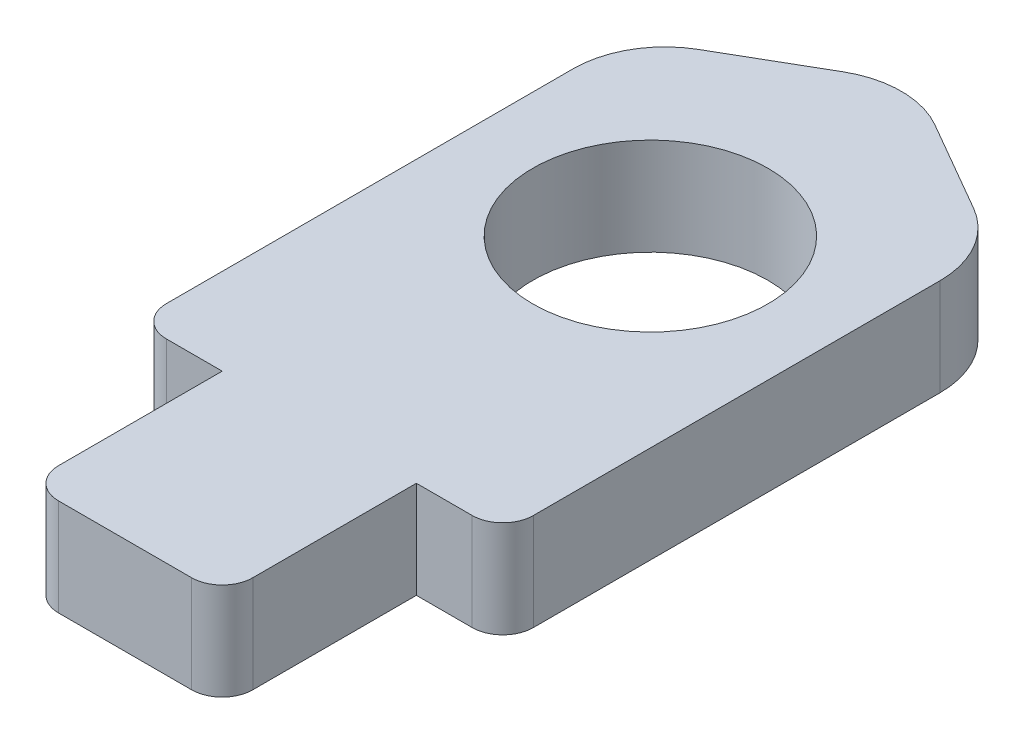
SolidWorks part; units mm, degrees
material "Beech"
ref_plane "Front Plane" through (0, 0, 0) normal (0, 0, 1) x (1, 0, 0)
ref_plane "Top Plane" through (0, 0, 0) normal (0, 1, 0) x (1, 0, 0)
ref_plane "Right Plane" through (0, 0, 0) normal (1, 0, 0) x (0, 0, -1)
sketch "Sketch2" plane through (0, 0, 0) normal (0, 1, 0) x (1, 0, 0)
  line L0 (-6, 5.205) -> (-5.4495, 5.205)
  line L1 (-6, 3.4729) -> (-6, -10.8257)
  line L2 (6, 3.4729) -> (6, -10.8257)
  line L3 (-6, -10.8257) -> (-3.175, -10.8257)
  line L4 (-4.5, 6.071) -> (-1.5, 7.8031)
  line L5 (-3.175, -10.8257) -> (-3.175, -17.1757)
  line L6 (-3.175, -17.1757) -> (3.175, -17.1757)
  line L7 (3.175, -17.1757) -> (3.175, -10.8257)
  line L8 (1.5, 7.8031) -> (4.5, 6.071)
  line L9 (3.175, -10.8257) -> (6, -10.8257)
  line L12 (5.4495, 5.205) -> (6, 5.205)
  circle A0 centre (0, 0) radius 3.845
  arc A1 (-4.5, 6.071) -> (-6, 3.4729) centre (-3, 3.4729) ccw
  arc A2 (4.5, 6.071) -> (6, 3.4729) centre (3, 3.4729) cw
  arc A3 (1.5, 7.8031) -> (-1.5, 7.8031) centre (0, 5.205) ccw
  point P3 (0, 5.205)
  point P14 (0, -17.1757)
  dimension "D1" = 7.69
  dimension "D9" = 3
  dimension "D10" = 3
  dimension "D11" = 3
  dimension "D2" = 5.205
  dimension "D3" = 16.0307
  dimension "D4" = 12
  dimension "D5" = 6.35
  dimension "D6" = 6.35
  dimension "D8" = 30
extrude "MotorMount_Extrude" add sketch "Sketch2" along normal blind 3.175 contours L8 A3 L4 A1 L1 L5 L2 A2 A0 region at (0, 0, 4.7761)
fillet "MotorMount_CornerFillet" radius 1 4 edges at (6, 1.5875, 10.8257) (-6, 1.5875, 10.8257) (-3.175, 1.5875, 17.1757) (3.175, 1.5875, 17.1757)
equation "\"CageLeftBottomEdge\"=22.11mm"
equation "\"CageLeftTopEdge\"=22.11mm"
equation "\"CageRightBottomEdge\"=21.63mm"
equation "\"CageRightTopEdge\"=21.63mm"
equation "\"CageHeight\"=86.04mm"
equation "\"CageLength\"=73.76mm"
equation "\"CageTopScrewClearance\"=10mm"
equation "\"CageBottomScrewClearance\"=25mm"
equation "\"CageLeftTopDepth\"= 11.65mm"
equation "\"CageLeftBottomDepth\"=11.11mm"
equation "\"CageLeftTopHeight\"=8.56175mm"
equation "\"CageLeftBottomHeight\"=16mm"
equation "\"CageRightTopDepth\"= 11.05mm"
equation "\"CageRightBottomDepth\"=10.58mm"
equation "\"CageRightTopHeight\"=9.6mm"
equation "\"CageRightBottomHeight\"=15.49mm"
equation "\"CageLeftTopChannelDepth\"=2.41908mm"
equation "\"CageLeftBottomChannelDepth\"=2.588mm"
equation "\"CageLeftChannelHeight\"=11.7mm"
equation "\"CageRightTopChannelDepth\"=2.32mm"
equation "\"CageRightBottomChannelDepth\"=2.318mm"
equation "\"CageRightChannelHeight\"=10mm"
equation "\"CageChanRelHeight\"=23.99mm"
equation "\"CageChanRelDepth\"=5.492mm"
equation "\"CageChamberRadius\"=16.261mm"
equation "\"CageScrewDiameter\"=4.8mm"
equation "\"CageSetScrewDiameter\"=3.5mm"
equation "\"CageAxleRadius\"=6.639mm"
equation "\"CageAxleKeyHeight\"=1.619mm"
equation "\"CageAxleKeyWidth\"=2.662mm"
equation "\"CageHoseWindowWidth\"=16.29mm"
equation "\"CageHoseWindowHeight\"=26.5mm"
equation "\"CageHoseWindow-Edge\"=8.89mm"
equation "\"CageScrew-VerticalEdge\"=5.0mm"
equation "\"CageScrew-HorizontalEdge\"=7.5mm"
equation "\"CageScrew-HoseCornerScrewEdge\"=4.45mm"
equation "\"CageAxle-BottomEdge\"=56.05mm"
equation "\"CageAxle-FrontEdge\"=46.03mm"
equation "\"CageBackSetScrew-Axle\"=40mm"
equation "\"CageFrontSetScrew-Axle\"=22mm"
equation "\"CageVelocityWindow-BackEdge\"=34.8mm"
equation "\"CageVelocityWindow-BottomEdge\"=27.55mm"
equation "\"CageVelocityWindowHeight\"=22.29mm"
equation "\"CageVelocityWindowWidth\"=12.61mm"
equation "\"TriggerSlot-BottomEdge\"=6.35mm"
equation "\"TriggerSlot-FrontEdge\"=15mm"
equation "\"TriggerSlotSize\"=6.7mm"
equation "\"TriggerRackOffset\"=.236224in"
equation "\"TriggerSlotSizeInt\"=.25in"
equation "\"MotorMountLegLength\"=.25in"
equation "\"GearOffset\"=.264907in"
equation "\"TriggerSlotSpacing\"=.25in"
equation "\"TGMGearFaceDiameter\"=24.40mm"
equation "\"TGMCylinderLength\"=15.00mm"
equation "\"TGMScrewHole-Center\"=8.70mm"
equation "\"TGMScrewHoleDiameter\"=5.04mm"
equation "\"TGMCenterHoleDiameter\"=9.50mm"
equation "\"TGMShaftCollarSideLength\"=19.00mm"
equation "\"TGMShaftCollarDockingDepth\"=7.00mm"
equation "\"whitemotordepth\"=11.27mm"
equation "\"whitemotorbackdepth\"=3.845mm"
equation "\"whitemotoraxledepth\" = 3.5mm"
equation "\"whitemotoraxleoffset\"=11.4mm"
equation "\"whitemotorwidth\"=12.07mm"
equation "\"whitemotorheight\"=16.68mm"
equation "\"whitemotorcylinderlength\" =13.04mm"
equation "\"whitemotorcylinderradius\"=3.845mm"
equation "\"whitemotorcylinderoffset\"=2.35mm"
equation "\"whitemotorcutoutlength\"=1.88mm"
equation "\"whitemotorouterrad\"=5mm"
equation "\"whitemotorinnerrad\"=2.95mm"
equation "\"D1@Sketch2\"=\"whitemotorcylinderradius\"*2"
equation "\"D2@Sketch2\"=\"whitemotoraxleoffset\"-\"whitemotorcylinderradius\"-\"whitemotorcylinderoffset\""
equation "\"D3@Sketch2\"=\"elasticdepth\"+.005in+\"TriggerRackOffset\"+\"GearOffset\""
equation "\"D5@Sketch2\"=\"TriggerSlotSizeInt\""
equation "\"D6@Sketch2\"=\"MotorMountLegLength\""
equation "\"motormountwidth\"=12"
equation "\"D4@Sketch2\"=\"motormountwidth\""
equation "\"TriggerMiniSlotWidth\"=3.5mm"
equation "\"TriggerRackWidth\"=6.5mm"
equation "\"elasticracklength\"=2in"
equation "\"elasticrackpegsize\"=.25in"
equation "\"elasticrackpegbuffer\"=.125in"
equation "\"elasticrackpegspacing\"=1.76476378in"
equation "\"elasticbaybuffer\"=.25in"
equation "\"elasticdepth\"=.125in"
equation "\"motormountcornerfillet\"=3mm"
equation "\"D10@Sketch2\"=\"motormountcornerfillet\""
